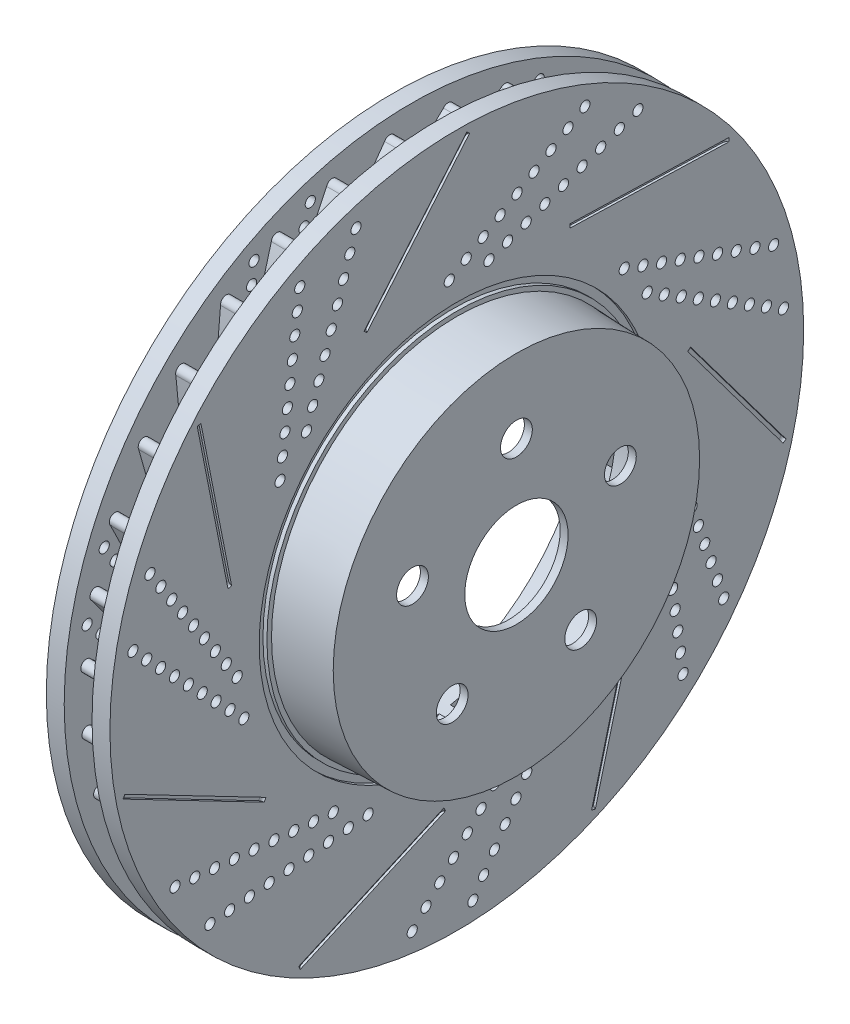
SolidWorks part; units mm, degrees
ref_plane "Front Plane" through (0, 0, 0) normal (0, 0, 1) x (1, 0, 0)
ref_plane "Top Plane" through (0, 0, 0) normal (0, 1, 0) x (1, 0, 0)
ref_plane "Right Plane" through (0, 0, 0) normal (1, 0, 0) x (0, 0, -1)
sketch "Sketch1" plane through (0, 0, 0) normal (1, 0, 0) x (0, 0, -1)
  circle A0 centre (0, 0) radius 87.27
  dimension "D1" = 174.54
extrude "Boss-Extrude1" add sketch "Sketch1" along normal blind 4.5
sketch "Sketch2" plane through (4.5, 0, 0) normal (1, 0, 0) x (0, 0, -1)
  circle A0 centre (0, 0) radius 49.72
  dimension "D1" = 99.44
extrude "Cut-Extrude1" cut sketch "Sketch2" against normal blind 4.5
sketch "Sketch3" plane through (4.5, 0, 0) normal (1, 0, 0) x (0, 0, -1)
  line L0 (0, 0) -> (0, -87.27) construction
  line L1 (-22.32, -50.7212) -> (-76.1786, -56.1065) construction
  line L2 (-31.0722, -45.884) -> (-87.2248, -40.6847) construction
  circle A0 centre (0, 0) radius 55.415 construction
  circle A1 centre (0, 0) radius 87.27 construction
  circle A2 centre (-22.32, -50.7212) radius 1.28
  circle A3 centre (-31.0722, -45.884) radius 1.28
  circle A4 centre (-27.2952, -51.2187) radius 1.28
  circle A5 centre (-32.2704, -51.7161) radius 1.28
  circle A6 centre (-37.2456, -52.2136) radius 1.28
  circle A7 centre (-42.2208, -52.7111) radius 1.28
  circle A8 centre (-47.196, -53.2085) radius 1.28
  circle A9 centre (-52.1711, -53.706) radius 1.28
  circle A10 centre (-57.1463, -54.2035) radius 1.28
  circle A11 centre (-62.1215, -54.7009) radius 1.28
  circle A12 centre (-36.0509, -45.423) radius 1.28
  circle A13 centre (-41.0296, -44.962) radius 1.28
  circle A14 centre (-46.0083, -44.501) radius 1.28
  circle A15 centre (-50.987, -44.04) radius 1.28
  circle A16 centre (-55.9657, -43.5791) radius 1.28
  circle A17 centre (-60.9444, -43.1181) radius 1.28
  circle A18 centre (-65.9231, -42.6571) radius 1.28
  circle A19 centre (-70.9019, -42.1961) radius 1.28
  dimension "D1" = 110.83
  dimension "D2" = 2.56
  dimension "D3" = 10
  dimension "D4" = 22.32
  dimension "D5" = 84.29
  dimension "D6" = 95.29
  dimension "D7" = 9
  dimension "D8" = 9
extrude "Cut-Extrude2" cut sketch "Sketch3" against normal blind 4.5
pattern_circular "CirPattern1" count 7 over 360 about axis through (0, 0, 0) along (1, 0, 0) of "Cut-Extrude2"
sketch "Sketch4" plane through (4.5, 0, 0) normal (1, 0, 0) x (0, 0, -1)
  line L0 (0, 0) -> (0, -87.27) construction
  line L1 (-3.2223, -58.8401) -> (-2.84, -59.6988)
  line L2 (-3.2223, -58.8401) -> (-39.7642, -75.1096)
  line L3 (-2.84, -59.6988) -> (-39.3818, -75.9683)
  line L4 (-39.7642, -75.1096) -> (-39.3818, -75.9683)
  circle A0 centre (0, 0) radius 87.27 construction
  dimension "D1" = 2.84
  dimension "D2" = 66
  dimension "D3" = 0.94
  dimension "D4" = 40
extrude "Cut-Extrude3" cut sketch "Sketch4" against normal blind 0.6
fillet "Fillet1" radius 1 2 edges at (3.9, -59.2695, 3.0312) (3.9, -75.5389, 39.573)
pattern_circular "CirPattern2" count 7 over 360 about axis through (0, 0, 0) along (1, 0, 0) of "Fillet1", "Cut-Extrude3"
ref_plane "Plane1" through (-3.5, 0, 0) normal (-1, 0, 0) x (0, 0, 1)
mirror "Mirror2" about plane through (-3.5, 0, 0) normal (-1, 0, 0) of bodies 106
sketch "Sketch6" plane through (-7, 0, 0) normal (1, 0, 0) x (0, 0, -1)
  line L0 (0, 0) -> (0, -87.27) construction
  circle A0 centre (0, 0) radius 87.27 construction
  circle A1 centre (0, 0) radius 49.72 construction
  arc A2 (-65.4085, -48.076) -> (-65.0267, -50.9082) centre (-65.2176, -49.4921) ccw
  arc A4 (-19.1997, -45.8634) -> (-16.5071, -46.8998) centre (0, 0) ccw
  arc A5 (-72.9416, -35.6242) -> (-73.0717, -38.4792) centre (-73.0067, -37.0517) ccw
  arc A6 (-27.0804, -41.6981) -> (-24.6161, -43.1987) centre (0, 0) ccw
  arc A7 (-78.1304, -22.0275) -> (-78.7682, -24.8133) centre (-78.4493, -23.4204) ccw
  arc A8 (-34.0907, -36.1926) -> (-31.9339, -38.1091) centre (0, 0) ccw
  arc A9 (-80.808, -7.7228) -> (-81.9329, -10.35) centre (-81.3704, -9.0364) ccw
  arc A10 (-40.0053, -29.5239) -> (-38.2254, -31.7946) centre (0, 0) ccw
  arc A11 (-80.8883, 6.8301) -> (-82.4643, 4.4461) centre (-81.6763, 5.6381) ccw
  arc A12 (-44.634, -21.9062) -> (-43.2882, -24.4583) centre (0, 0) ccw
  arc A13 (-78.3688, 21.1635) -> (-80.3452, 19.0992) centre (-79.357, 20.1314) ccw
  arc A14 (-47.8283, -13.5844) -> (-46.9598, -16.3358) centre (0, 0) ccw
  arc A15 (-73.3305, 34.8167) -> (-75.6437, 33.1384) centre (-74.4871, 33.9776) ccw
  arc A16 (-49.4852, -4.8261) -> (-49.122, -7.6883) centre (0, 0) ccw
  arc A17 (-65.9353, 47.3509) -> (-68.511, 46.1126) centre (-67.2231, 46.7317) ccw
  arc A18 (-49.5517, 4.0874) -> (-49.7054, 1.2063) centre (0, 0) ccw
  arc A19 (-56.4209, 58.3631) -> (-59.1763, 57.6046) centre (-57.7986, 57.9839) ccw
  arc A20 (-48.0255, 12.8695) -> (-48.6912, 10.0622) centre (0, 0) ccw
  arc A21 (-45.093, 67.4995) -> (-47.9396, 67.2452) centre (-46.5163, 67.3724) ccw
  arc A22 (-44.9558, 21.238) -> (-46.112, 18.5946) centre (0, 0) ccw
  arc A23 (-32.3159, 74.4665) -> (-35.1621, 74.7245) centre (-33.739, 74.5955) ccw
  arc A24 (-40.4412, 28.9239) -> (-42.0508, 26.5294) centre (0, 0) ccw
  arc A25 (-18.5, 79.04) -> (-21.2544, 79.8021) centre (-19.8772, 79.421) ccw
  arc A26 (-34.6267, 35.6801) -> (-36.638, 33.6115) centre (0, 0) ccw
  arc A27 (-4.0896, 81.0731) -> (-6.6636, 82.3148) centre (-5.3766, 81.6939) ccw
  arc A28 (-27.6993, 41.2896) -> (-30.0476, 39.6134) centre (0, 0) ccw
  arc A29 (10.4523, 80.5004) -> (8.1413, 82.1818) centre (9.2968, 81.3411) ccw
  arc A30 (-19.8816, 45.5719) -> (-22.4915, 44.342) centre (0, 0) ccw
  arc A31 (24.6582, 77.3404) -> (22.6846, 79.4074) centre (23.6714, 78.3739) ccw
  arc A32 (-11.4249, 48.3896) -> (-14.2125, 47.6454) centre (0, 0) ccw
  arc A33 (38.0716, 71.6946) -> (36.4988, 74.0808) centre (37.2852, 72.8877) ccw
  arc A34 (-2.601, 49.6519) -> (-5.4767, 49.4174) centre (0, 0) ccw
  arc A35 (50.2614, 63.7445) -> (49.1399, 66.3732) centre (49.7006, 65.0588) ccw
  arc A36 (6.3064, 49.3184) -> (3.4351, 49.6012) centre (0, 0) ccw
  arc A37 (60.8357, 53.7456) -> (60.2016, 56.5322) centre (60.5186, 55.1389) ccw
  arc A38 (15.0112, 47.3998) -> (12.2366, 48.1907) centre (0, 0) ccw
  arc A39 (69.4547, 42.0193) -> (69.3283, 44.8743) centre (69.3915, 43.4468) ccw
  arc A40 (23.2336, 43.9577) -> (20.6447, 45.2313) centre (0, 0) ccw
  arc A41 (75.8413, 28.9424) -> (76.2268, 31.7741) centre (76.0341, 30.3583) ccw
  arc A42 (30.7091, 39.1028) -> (28.3893, 40.8182) centre (0, 0) ccw
  arc A43 (79.7904, 14.9353) -> (80.6753, 17.6527) centre (80.2329, 16.294) ccw
  arc A44 (37.1977, 32.991) -> (35.2215, 35.0931) centre (0, 0) ccw
  arc A45 (81.1749, 0.4481) -> (82.5308, 2.9639) centre (81.8529, 1.706) ccw
  arc A46 (42.4907, 25.819) -> (40.9215, 28.2401) centre (0, 0) ccw
  arc A47 (79.9504, -14.0534) -> (81.7338, -11.8202) centre (80.8421, -12.9368) ccw
  arc A48 (46.418, 17.817) -> (45.3064, 20.4795) centre (0, 0) ccw
  arc A49 (76.1563, -28.1033) -> (78.3097, -26.2244) centre (77.233, -27.1638) ccw
  arc A50 (48.8534, 9.2424) -> (48.2351, 12.0606) centre (0, 0) ccw
  arc A51 (69.9144, -41.2499) -> (72.3687, -39.7857) centre (71.1415, -40.5178) ccw
  arc A52 (49.7186, 0.3708) -> (49.6134, 3.2541) centre (0, 0) ccw
  arc A53 (61.4254, -53.0706) -> (64.1017, -52.0682) centre (62.7635, -52.5694) ccw
  arc A54 (48.9858, -8.5128) -> (49.3971, -5.657) centre (0, 0) ccw
  arc A55 (50.9621, -63.1857) -> (53.7744, -62.6773) centre (52.3683, -62.9315) ccw
  arc A56 (46.6786, -17.1227) -> (47.5932, -14.3863) centre (0, 0) ccw
  arc A57 (38.8609, -71.2699) -> (41.7188, -71.2718) centre (40.2898, -71.2709) ccw
  arc A58 (42.8711, -25.1823) -> (44.2596, -22.6532) centre (0, 0) ccw
  arc A59 (25.5106, -77.0635) -> (28.3222, -77.5756) centre (26.9164, -77.3195) ccw
  arc A60 (37.6856, -32.4326) -> (39.5034, -30.192) centre (0, 0) ccw
  arc A61 (11.3405, -80.3801) -> (14.0154, -81.3861) centre (12.678, -80.8831) ccw
  arc A62 (31.289, -38.6404) -> (33.4776, -36.7604) centre (0, 0) ccw
  arc A63 (-3.1942, -81.1133) -> (-0.7418, -82.5807) centre (-1.968, -81.847) ccw
  arc A64 (23.8866, -43.6063) -> (26.3758, -42.1473) centre (0, 0) ccw
  arc A65 (-17.6262, -79.2394) -> (-15.4753, -81.1211) centre (-16.5507, -80.1803) ccw
  arc A66 (15.7166, -47.1706) -> (18.4262, -46.1796) centre (0, 0) ccw
  arc A67 (-31.4917, -74.8187) -> (-29.7113, -77.0543) centre (-30.6015, -75.9365) ccw
  arc A68 (7.0413, -49.2189) -> (9.8844, -48.7276) centre (0, 0) ccw
  arc A69 (-44.345, -67.9933) -> (-42.9924, -70.5108) centre (-43.6687, -69.2521) ccw
  arc A70 (-1.8602, -49.6852) -> (1.0249, -49.7094) centre (0, 0) ccw
  arc A71 (-55.773, -58.9825) -> (-54.8917, -61.7011) centre (-55.3324, -60.3418) ccw
  arc A72 (-10.7019, -48.5546) -> (-7.8675, -49.0936) centre (0, 0) ccw
  spline S0 degree 2 poles (-16.5071, -46.8998) (-40.4607, -52.4329) (-65.0267, -50.9082) knots 0 0 0 1 1 1
  spline S1 degree 3 poles (-19.1997, -45.8634) (-36.5418, -49.2713) (-43.6513, -48.4557) (-65.4085, -48.076) knots 0 0 0 0 1 1 1 1
  spline S2 degree 3 poles (-27.0804, -41.6981) (-44.7523, -41.9547) (-51.6019, -39.8827) (-72.9416, -35.6242) knots 0 0 0 0 1 1 1 1
  spline S3 degree 2 poles (-24.6161, -43.1987) (-49.1727, -44.3658) (-73.0717, -38.4792) knots 0 0 0 1 1 1
  spline S4 degree 3 poles (-34.0907, -36.1926) (-51.5244, -33.2896) (-57.894, -30.0279) (-78.1304, -22.0275) knots 0 0 0 0 1 1 1 1
  spline S5 degree 2 poles (-31.9339, -38.1091) (-56.3043, -34.8727) (-78.7682, -24.8133) knots 0 0 0 1 1 1
  spline S6 degree 3 poles (-40.0053, -29.5239) (-56.6405, -23.5546) (-62.3253, -19.208) (-80.808, -7.7228) knots 0 0 0 0 1 1 1 1
  spline S7 degree 2 poles (-38.2254, -31.7946) (-61.6262, -24.2587) (-81.9329, -10.35) knots 0 0 0 1 1 1
  spline S8 degree 3 poles (-44.634, -21.9062) (-59.9361, -13.0625) (-64.7534, -7.7707) (-80.8883, 6.8301) knots 0 0 0 0 1 1 1 1
  spline S9 degree 2 poles (-43.2882, -24.4583) (-64.9674, -12.8651) (-82.4643, 4.4461) knots 0 0 0 1 1 1
  spline S10 degree 3 poles (-47.8283, -13.5844) (-61.3053, -2.1506) (-65.1003, 3.9164) (-78.3688, 21.1635) knots 0 0 0 0 1 1 1 1
  spline S11 degree 2 poles (-46.9598, -16.3358) (-66.2205, -1.058) (-80.3452, 19.0992) knots 0 0 0 1 1 1
  spline S12 degree 3 poles (-49.4852, -4.8261) (-60.7041, 8.8304) (-63.3549, 15.4775) (-73.3305, 34.8167) knots 0 0 0 0 1 1 1 1
  spline S13 degree 2 poles (-49.122, -7.6883) (-65.3453, 10.7832) (-75.6437, 33.1384) knots 0 0 0 1 1 1
  spline S14 degree 3 poles (-49.5517, 4.0874) (-58.1518, 19.5276) (-59.5731, 26.5412) (-65.9353, 47.3509) knots 0 0 0 0 1 1 1 1
  spline S15 degree 2 poles (-49.7054, 1.2063) (-62.3697, 22.2777) (-68.511, 46.1126) knots 0 0 0 1 1 1
  spline S16 degree 3 poles (-48.0255, 12.8695) (-53.7305, 29.5972) (-53.8766, 36.7519) (-56.4209, 58.3631) knots 0 0 0 0 1 1 1 1
  spline S17 degree 2 poles (-48.6912, 10.0622) (-57.3896, 33.0563) (-59.1763, 57.6046) knots 0 0 0 1 1 1
  spline S18 degree 3 poles (-44.9558, 21.238) (-47.5822, 38.7155) (-46.4485, 45.7813) (-45.093, 67.4995) knots 0 0 0 0 1 1 1 1
  spline S19 degree 2 poles (-46.112, 18.5946) (-50.5649, 42.7723) (-47.9396, 67.2452) knots 0 0 0 1 1 1
  spline S20 degree 3 poles (-40.4412, 28.9239) (-39.9046, 46.5895) (-37.5275, 53.3393) (-32.3159, 74.4665) knots 0 0 0 0 1 1 1 1
  spline S21 degree 2 poles (-42.0508, 26.5294) (-42.115, 51.1137) (-35.1621, 74.7245) knots 0 0 0 1 1 1
  spline S22 degree 3 poles (-34.6267, 35.6801) (-30.9445, 52.966) (-27.4003, 59.1829) (-18.5, 79.04) knots 0 0 0 0 1 1 1 1
  spline S23 degree 2 poles (-36.638, 33.6115) (-32.3115, 57.8122) (-21.2544, 79.8021) knots 0 0 0 1 1 1
  spline S24 degree 3 poles (-27.6993, 41.2896) (-20.9897, 57.6402) (-16.3924, 63.1243) (-4.0896, 81.0731) knots 0 0 0 0 1 1 1 1
  spline S25 degree 2 poles (-30.0476, 39.6134) (-21.4695, 62.6525) (-6.6636, 82.3148) knots 0 0 0 1 1 1
  spline S26 degree 3 poles (-19.8816, 45.5719) (-10.3604, 60.4618) (-4.8577, 65.0369) (10.4523, 80.5004) knots 0 0 0 0 1 1 1 1
  spline S27 degree 2 poles (-22.4915, 44.342) (-9.9374, 65.4792) (8.1413, 82.1818) knots 0 0 0 1 1 1
  spline S28 degree 3 poles (-11.4249, 48.3896) (0.602, 61.34) (6.8331, 64.8591) (24.6582, 77.3404) knots 0 0 0 0 1 1 1 1
  spline S29 degree 2 poles (-14.2125, 47.6454) (1.9141, 66.2013) (22.6846, 79.4074) knots 0 0 0 1 1 1
  spline S30 degree 3 poles (-2.601, 49.6519) (11.545, 60.2468) (18.3043, 62.5967) (38.0716, 71.6946) knots 0 0 0 0 1 1 1 1
  spline S31 degree 2 poles (-5.4767, 49.4174) (13.704, 64.7957) (36.4988, 74.0808) knots 0 0 0 1 1 1
  spline S32 degree 3 poles (6.3064, 49.3184) (22.1169, 57.2171) (29.1873, 58.3223) (50.2614, 63.7445) knots 0 0 0 0 1 1 1 1
  spline S33 degree 2 poles (3.4351, 49.6012) (25.0535, 61.3074) (49.1399, 66.3732) knots 0 0 0 1 1 1
  spline S34 degree 3 poles (15.0112, 47.3998) (31.978, 52.3485) (39.1321, 52.1735) (60.8357, 53.7456) knots 0 0 0 0 1 1 1 1
  spline S35 degree 2 poles (12.2366, 48.1907) (35.5977, 55.8487) (60.2016, 56.5322) knots 0 0 0 1 1 1
  spline S36 degree 3 poles (23.2336, 43.9577) (40.8113, 45.7974) (47.8191, 44.3477) (69.4547, 42.0193) knots 0 0 0 0 1 1 1 1
  spline S37 degree 2 poles (20.6447, 45.2313) (44.9978, 48.595) (69.3283, 44.8743) knots 0 0 0 1 1 1
  spline S38 degree 3 poles (30.7091, 39.1028) (48.3329, 37.7742) (54.9693, 35.0966) (75.8413, 28.9424) knots 0 0 0 0 1 1 1 1
  spline S39 degree 2 poles (28.3893, 40.8182) (52.9517, 39.7794) (76.2268, 31.7741) knots 0 0 0 1 1 1
  spline S40 degree 3 poles (37.1977, 32.991) (54.301, 28.537) (60.3526, 24.7175) (79.7904, 14.9353) knots 0 0 0 0 1 1 1 1
  spline S41 degree 2 poles (35.2215, 35.0931) (59.2036, 29.6852) (80.6753, 17.6527) knots 0 0 0 1 1 1
  spline S42 degree 3 poles (42.4907, 25.819) (58.5239, 18.3826) (63.7962, 13.5439) (81.1749, 0.4481) knots 0 0 0 0 1 1 1 1
  spline S43 degree 2 poles (40.9215, 28.2401) (63.5527, 18.6369) (82.5308, 2.9639) knots 0 0 0 1 1 1
  spline S44 degree 3 poles (46.418, 17.817) (60.8657, 7.6373) (65.1893, 1.935) (79.9504, -14.0534) knots 0 0 0 0 1 1 1 1
  spline S45 degree 2 poles (45.3064, 20.4795) (65.8591, 6.9897) (81.7338, -11.8202) knots 0 0 0 1 1 1
  spline S46 degree 3 poles (48.8534, 9.2424) (61.2513, -3.3534) (64.4872, -9.7361) (76.1563, -28.1033) knots 0 0 0 0 1 1 1 1
  spline S47 degree 2 poles (48.2351, 12.0606) (66.0488, -4.8823) (78.3097, -26.2244) knots 0 0 0 1 1 1
  spline S48 degree 3 poles (49.7186, 0.3708) (59.6681, -14.2363) (61.7124, -21.0943) (69.9144, -41.2499) knots 0 0 0 0 1 1 1 1
  spline S49 degree 2 poles (49.6134, 3.2541) (64.1156, -16.5973) (72.3687, -39.7857) knots 0 0 0 1 1 1
  spline S50 degree 3 poles (48.9858, -8.5128) (56.1673, -24.6617) (56.9541, -31.7745) (61.4254, -53.0706) knots 0 0 0 0 1 1 1 1
  spline S51 degree 2 poles (49.3971, -5.657) (60.1217, -27.7788) (64.1017, -52.0682) knots 0 0 0 1 1 1
  spline S52 degree 3 poles (46.6786, -17.1227) (50.8611, -34.2944) (50.3653, -41.4334) (50.9621, -63.1857) knots 0 0 0 0 1 1 1 1
  spline S53 degree 2 poles (47.5932, -14.3863) (54.1954, -38.0675) (53.7744, -62.6773) knots 0 0 0 1 1 1
  spline S54 degree 3 poles (42.8711, -25.1823) (43.9202, -42.8249) (42.1577, -49.7606) (38.8609, -71.2699) knots 0 0 0 0 1 1 1 1
  spline S55 degree 2 poles (44.2596, -22.6532) (46.5272, -47.1327) (41.7188, -71.2718) knots 0 0 0 1 1 1
  spline S56 degree 3 poles (37.6856, -32.4326) (35.5677, -49.979) (32.5951, -56.4885) (25.5106, -77.0635) knots 0 0 0 0 1 1 1 1
  spline S57 degree 2 poles (39.5034, -30.192) (37.3636, -54.6831) (28.3222, -77.5756) knots 0 0 0 1 1 1
  spline S58 degree 3 poles (31.289, -38.6404) (26.0721, -55.5267) (21.9849, -61.4008) (11.3405, -80.3801) knots 0 0 0 0 1 1 1 1
  spline S59 degree 2 poles (33.4776, -36.7604) (26.9992, -60.4758) (14.0154, -81.3861) knots 0 0 0 1 1 1
  spline S60 degree 3 poles (23.8866, -43.6063) (15.7384, -59.2897) (10.668, -64.3396) (-3.1942, -81.1133) knots 0 0 0 0 1 1 1 1
  spline S61 degree 2 poles (26.3758, -42.1473) (15.7669, -64.3248) (-0.7418, -82.5807) knots 0 0 0 1 1 1
  spline S62 degree 3 poles (15.7166, -47.1706) (4.8989, -61.1471) (-0.9917, -65.2105) (-17.6262, -79.2394) knots 0 0 0 0 1 1 1 1
  spline S63 degree 2 poles (18.4262, -46.1796) (4.0279, -66.1064) (-15.4753, -81.1211) knots 0 0 0 1 1 1
  spline S64 degree 3 poles (7.0413, -49.2189) (-6.098, -61.0391) (-12.6195, -63.9855) (-31.4917, -74.8187) knots 0 0 0 0 1 1 1 1
  spline S65 degree 2 poles (9.8844, -48.7276) (-7.8406, -65.7632) (-29.7113, -77.0543) knots 0 0 0 1 1 1
  spline S66 degree 3 poles (-1.8602, -49.6852) (-16.899, -58.9694) (-23.8418, -60.7039) (-44.345, -67.9933) knots 0 0 0 0 1 1 1 1
  spline S67 degree 2 poles (1.0249, -49.7094) (-19.4571, -63.3064) (-42.9924, -70.5108) knots 0 0 0 1 1 1
  spline S68 degree 3 poles (-10.7019, -48.5546) (-27.1568, -55.0043) (-34.2977, -55.4712) (-55.773, -58.9825) knots 0 0 0 0 1 1 1 1
  spline S69 degree 2 poles (-7.8675, -49.0936) (-30.4482, -58.8148) (-54.8917, -61.7011) knots 0 0 0 1 1 1
  point P257 (0, 0)
  dimension "D1" = 35
extrude "Boss-Extrude2" add sketch "Sketch6" along normal blind 7
sketch "Sketch8" plane through (0, 0, 0) normal (0, 0, 1) x (1, 0, 0)
  line L0 (0, 51.7708) -> (0, 44.7708)
  line L1 (0, 71.6946) -> (0, 49.6519) construction
  line L2 (0, 44.7708) -> (17.5, 44.1597)
  line L3 (17.5, 44.1597) -> (17.5, 0)
  line L4 (0, 51.7708) -> (3.5, 51.7708)
  line L5 (3.5, 51.7708) -> (3.5, 47.7708)
  line L6 (3.5, 47.7708) -> (4.5, 47.7708)
  line L7 (4.5, -49.72) -> (4.5, 49.72) construction
  line L8 (4.5, 47.7708) -> (4.5, 46.6149)
  line L9 (4.5, 46.6149) -> (19.5, 46.0911)
  line L10 (19.5, 46.0911) -> (19.5, 0)
  line L11 (0, 44.7708) -> (24.89, 44.7708) construction
  line L12 (17.5, 0) -> (19.5, 0)
  line L13 (0, 0) -> (36.2527, 0) construction
  dimension "D1" = 2
  dimension "D2" = 2
  dimension "D3" = 15
  dimension "D4" = 44.4
  dimension "D5" = 2
  dimension "D6" = 7
  dimension "D7" = 4
  dimension "D8" = 1
revolve "Revolve1" add sketch "Sketch8" angle 360 about L13
sketch "Sketch9" plane through (19.5, 0, 0) normal (1, 0, 0) x (0, 0, -1)
  circle A0 centre (0, 0) radius 27.5 construction
  circle A1 centre (0, 0) radius 13
  circle A2 centre (0, 27.5) radius 4
  circle A3 centre (0, 0) radius 27.5 construction
  circle A4 centre (26.1541, 8.498) radius 4
  circle A5 centre (0, 0) radius 27.5 construction
  circle A6 centre (16.1641, -22.248) radius 4
  circle A7 centre (0, 0) radius 27.5 construction
  circle A8 centre (-16.1641, -22.248) radius 4
  circle A9 centre (0, 0) radius 27.5 construction
  circle A10 centre (-26.1541, 8.498) radius 4
  point P21 (0, 0)
  dimension "D1" = 26
  dimension "D2" = 55
  dimension "D3" = 8
  dimension "D4" = 5
extrude "Cut-Extrude4" cut sketch "Sketch9" against normal blind 4.6
scale "Scale1" scale about centroid uniform scaling yes scale factor 2
